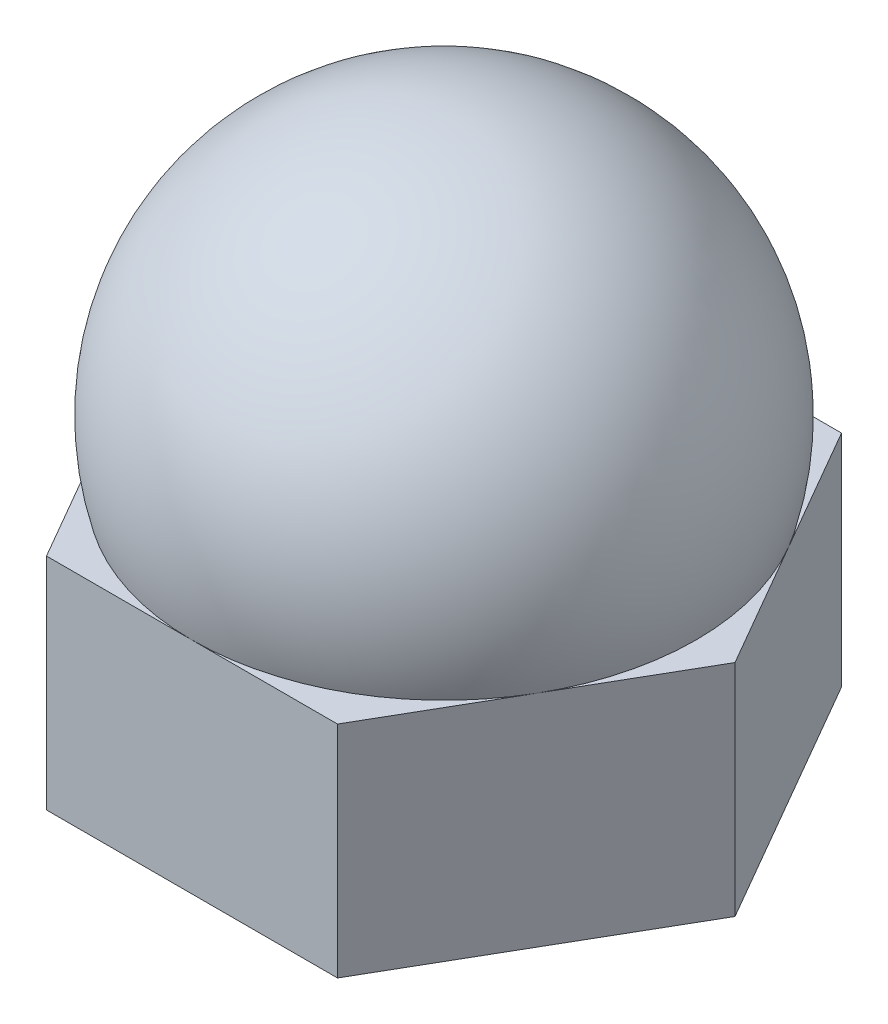
SolidWorks part; units mm, degrees
material "acero"
ref_plane "Alzado" through (0, 0, 0) normal (0, 0, 1) x (1, 0, 0)
ref_plane "Planta" through (0, 0, 0) normal (0, 1, 0) x (1, 0, 0)
ref_plane "Vista lateral" through (0, 0, 0) normal (1, 0, 0) x (0, 0, -1)
sketch "Croquis1" plane through (0, 0, 0) normal (0, 1, 0) x (1, 0, 0)
  line L1 (-1.5877, 2.75) -> (-3.1754, 0)
  line L2 (-3.1754, 0) -> (-1.5877, -2.75)
  line L3 (-1.5877, -2.75) -> (1.5877, -2.75)
  line L4 (1.5877, -2.75) -> (3.1754, 0)
  line L5 (3.1754, 0) -> (1.5877, 2.75)
  line L6 (1.5877, 2.75) -> (-1.5877, 2.75)
  circle A0 centre (0, 0) radius 2.75 construction
  circle A1 centre (0, 0) radius 1.25
  dimension "D1" = 2.5
  dimension "D2" = 5.5
extrude "Saliente-Extruir1" add sketch "Croquis1" along normal blind 2.4
sketch "Croquis3" plane through (0, 0, 0) normal (1, 0, 0) x (0, 0, -1)
  line L0 (-2.75, 0) -> (0, 0) construction
  line L1 (-2.75, 2.4) -> (2.75, 2.4)
  line L2 (0, 6) -> (0, 0) construction
  arc A0 (-2.75, 2.4) -> (2.75, 2.4) centre (0, 3.1497) cw
  point P3 (0, 6)
  dimension "D1" = 6
revolve "Revolución2" add sketch "Croquis3" angle 360 about L2 region at (0, 3.9659, 1.2592)
